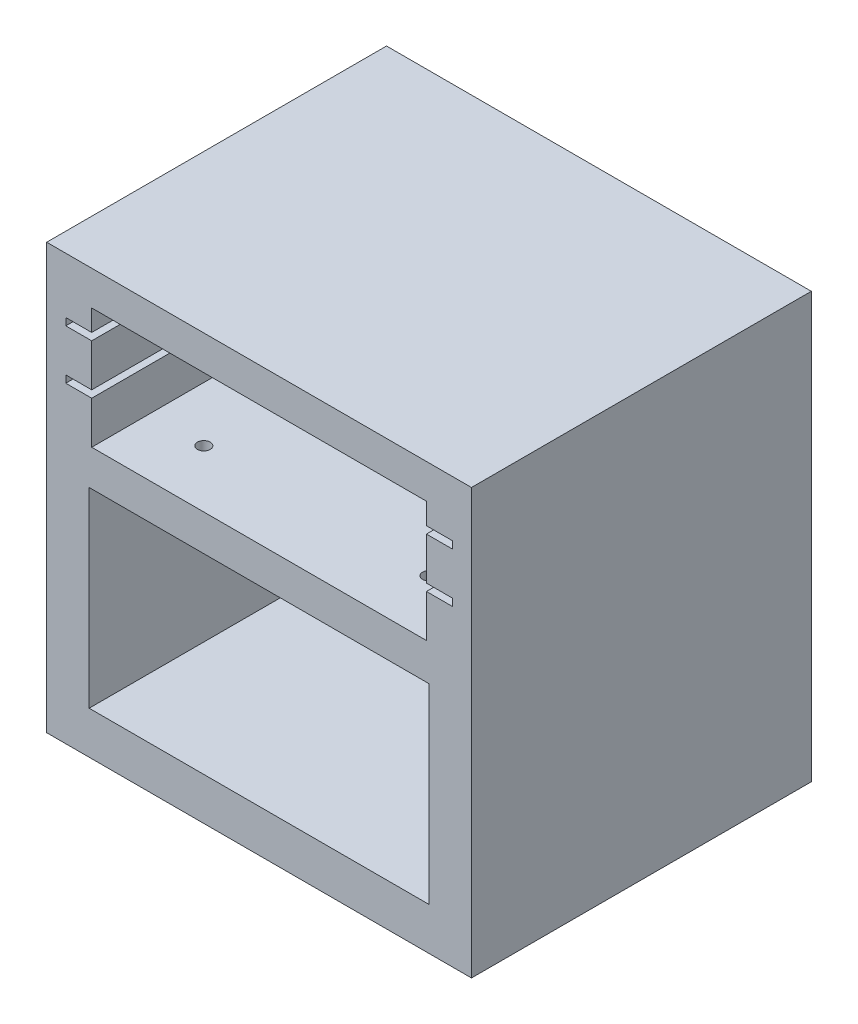
SolidWorks part; units mm, degrees
ref_plane "Front Plane" through (0, 0, 0) normal (0, 0, 1) x (1, 0, 0)
ref_plane "Top Plane" through (0, 0, 0) normal (0, 1, 0) x (1, 0, 0)
ref_plane "Right Plane" through (0, 0, 0) normal (1, 0, 0) x (0, 0, -1)
sketch "Planning Sketch" plane through (0, 0, 0) normal (0, 0, 1) x (1, 0, 0)
  line L0 (50, 35.2) -> (-50, 35.2)
  line L1 (-50, -50) -> (50, -50)
  line L2 (-50, -50) -> (-50, 50)
  line L3 (-50, 50) -> (50, 50)
  line L4 (50, -50) -> (50, 50)
  line L5 (-50, -50) -> (50, 50) construction
  line L6 (-50, 50) -> (50, -50) construction
  line L7 (50, 23.5) -> (-50, 23.5)
  line L8 (50, 23.5) -> (50, 25.2)
  line L9 (50, 25.2) -> (-50, 25.2)
  line L10 (-50, 23.5) -> (-50, 25.2)
  line L11 (50, 23.5) -> (-50, 25.2) construction
  line L12 (50, 25.2) -> (-50, 23.5) construction
  line L13 (50, 35.2) -> (50, 36.9)
  line L14 (50, 36.9) -> (-50, 36.9)
  line L15 (-50, 35.2) -> (-50, 36.9)
  line L16 (50, 35.2) -> (-50, 36.9) construction
  line L17 (50, 36.9) -> (-50, 35.2) construction
  line L22 (0, -50) -> (0, 50)
  line L23 (-50, 5) -> (50, 5)
  line L24 (-50, -10) -> (50, -10)
  line L25 (-50, -10) -> (-50, -40)
  line L26 (-50, -40) -> (50, -40)
  line L27 (50, -10) -> (50, -40)
  line L28 (-50, -10) -> (50, -40) construction
  line L29 (-50, -40) -> (50, -10) construction
  line L30 (-50, -5) -> (50, -5)
  line L31 (-50, -5) -> (-50, 13.5)
  line L32 (-50, 13.5) -> (50, 13.5)
  line L33 (50, -5) -> (50, 13.5)
  line L34 (-50, -5) -> (50, 13.5) construction
  line L35 (-50, 13.5) -> (50, -5) construction
  point P5 (0, -91.2675)
  point P6 (0, 24.35)
  point P12 (0, 36.05)
  point P17 (0, 0)
  point P19 (0, -25)
  point P26 (0, 4.25)
  point P31 (47.0241, 37.6779)
  point P32 (50, 37.543)
  point P33 (50, 10.907)
  point P34 (0, -34.4032)
  point P35 (50, 6.3114)
  point P36 (50, -15.5211)
  point P37 (50, 10.2943)
  point P38 (50, -12.7183)
  point P39 (50, -6.061)
  point P40 (0, 0)
  point P41 (0, 0)
  point P42 (0, 0)
  point P43 (50, -6.7465)
  dimension "D1" = 100
  dimension "D2" = 1.7
  dimension "D3" = 1.7
  dimension "D4" = 10
  dimension "D5" = 30
  dimension "D6" = 18.5
  dimension "D7" = 10
  dimension "D8" = 10
  dimension "D9" = 8.5
  dimension "D10" = 5
  dimension "D11" = 10
sketch "Mounting Sketch" plane through (0, 0, 0) normal (0, 0, 1) x (1, 0, 0)
  line L0 (50, 0) -> (-50, 0) construction
  line L2 (-50, -50) -> (-50, 50)
  line L4 (50, -50) -> (50, 50)
  line L5 (-50, -50) -> (50, 50) construction
  line L6 (-50, 50) -> (50, -50) construction
  line L7 (-50, 50) -> (50, 50)
  line L8 (39.4, 41.9) -> (-39.4, 41.9)
  line L9 (-39.4, 41.9) -> (-39.4, 36.9)
  line L10 (-39.4, 36.9) -> (-45.5, 36.9)
  line L11 (-45.5, 36.9) -> (-45.5, 35.2)
  line L12 (-45.5, 35.2) -> (-39.4, 35.2)
  line L13 (-39.4, 35.2) -> (-39.4, 25.2)
  line L14 (-39.4, 25.2) -> (-45.5, 25.2)
  line L15 (-45.5, 25.2) -> (-45.5, 23.5)
  line L16 (-45.5, 23.5) -> (-39.4, 23.5)
  line L19 (-50, 13.5) -> (50, 13.5) construction
  line L20 (-39.4, 13.5) -> (39.4, 13.5)
  line L21 (39.4, 13.5) -> (39.4, 23.5)
  line L22 (39.4, 23.5) -> (45.5, 23.5)
  line L23 (45.5, 23.5) -> (45.5, 25.2)
  line L24 (45.5, 25.2) -> (39.4, 25.2)
  line L25 (39.4, 25.2) -> (39.4, 35.2)
  line L26 (39.4, 35.2) -> (45.5, 35.2)
  line L27 (45.5, 35.2) -> (45.5, 36.9)
  line L28 (45.5, 36.9) -> (39.4, 36.9)
  line L29 (39.4, 36.9) -> (39.4, 41.9)
  line L31 (-50, -50) -> (50, -50)
  line L32 (-50, 5) -> (50, 5) construction
  line L33 (-40, 5) -> (-40, -40)
  line L34 (-40, -40) -> (40, -40)
  line L35 (40, -40) -> (40, 5)
  line L36 (0, -50) -> (0, 50) construction
  line L37 (-40, 5) -> (40, 5)
  line L38 (-39.4, 23.5) -> (-39.4, 13.5)
  point P0 (0, 0)
  point P13 (-38.4803, 13.5)
  point P14 (39.4736, 13.5)
  point P15 (0, 13.5)
  point P17 (-46.7402, 23.5)
  point P19 (46.2682, 21.8769)
  point P21 (46.903, 35.2)
  point P23 (0, 0)
  point P25 (0, 0)
  point P27 (0, 0)
  point P29 (0, 0)
  point P64 (0, -40)
  dimension "D1" = 10
  dimension "D2" = 80
  dimension "D3" = 10
  dimension "D4" = 1.7
  dimension "D5" = 45
  dimension "D6" = 5
  dimension "D7" = 91
  dimension "D8" = 78.8
extrude "Boss-Extrude3" add sketch "Mounting Sketch" along normal mid plane 80
sketch "Sketch10" plane through (0, 5, 0) normal (0, -1, 0) x (1, 0, 0)
  line L0 (26.5, 0) -> (-26.5, 0) construction
  line L1 (-5, -12) -> (5, -12)
  line L2 (-5, -12) -> (-5, 0)
  line L3 (-5, 0) -> (5, 0)
  line L4 (5, -12) -> (5, 0)
  line L5 (-5, -12) -> (5, 0) construction
  line L6 (-5, 0) -> (5, -12) construction
  line L7 (-38.25, -11.5) -> (-20.47, -11.5) construction
  line L8 (-38.25, -11.5) -> (-38.25, 3.74) construction
  line L9 (-38.25, 3.74) -> (-20.47, 3.74) construction
  line L10 (-20.47, -11.5) -> (-20.47, 3.74) construction
  line L11 (-38.25, -11.5) -> (-20.47, 3.74) construction
  line L12 (-38.25, 3.74) -> (-20.47, -11.5) construction
  line L13 (-26.5, -26.5) -> (26.5, -26.5) construction
  line L14 (-26.5, -26.5) -> (-26.5, 26.5) construction
  line L15 (-26.5, 26.5) -> (26.5, 26.5) construction
  line L16 (26.5, -26.5) -> (26.5, 26.5) construction
  line L17 (-26.5, -26.5) -> (26.5, 26.5) construction
  line L18 (-26.5, 26.5) -> (26.5, -26.5) construction
  line L19 (0, -6) -> (0, 0) construction
  circle A0 centre (0, 0) radius 7.75
  circle A1 centre (-20.47, 3.74) radius 2
  circle A2 centre (-38.25, -11.5) radius 2
  circle A3 centre (26.5, 26.5) radius 1.5
  circle A4 centre (26.5, -26.5) radius 1.5
  circle A5 centre (-26.5, -26.5) radius 1.5
  circle A6 centre (-26.5, 26.5) radius 1.5
  point P3 (0, -6)
  point P8 (-29.36, -3.88)
  point P15 (0, 0)
  line M4 (-40, 40) -> (-40, -40)
  dimension "D1" = 15.5
  dimension "D6" = 4
  dimension "D7" = 12
  dimension "D10" = 3
  dimension "D2" = 38.25
  dimension "D3" = 15.24
  dimension "D4" = 17.78
  dimension "D5" = 11.5
  dimension "D8" = 10
  dimension "D9" = 53
extrude "Cut-Extrude1" cut sketch "Sketch10" against normal up to next contours L4 A0 L2 L3 | L2 A0 L4 L3 | A0 L2 L1 L4 | A1 | A2 M4 | A2 M4 | A6 | A3 | A4 | A5 region at (0, 5, -9.5567) region at (0, 5, 2.2113) region at (0, 5, -3.6061) region at (-20.47, 5, 3.74) region at (-38.2006, 5, -11.5) region at (-40.1006, 5, -11.5) region at (26.5, 5, 26.5) region at (26.5, 5, -26.5) region at (-26.5, 5, -26.5) region at (-26.5, 5, 26.5)
